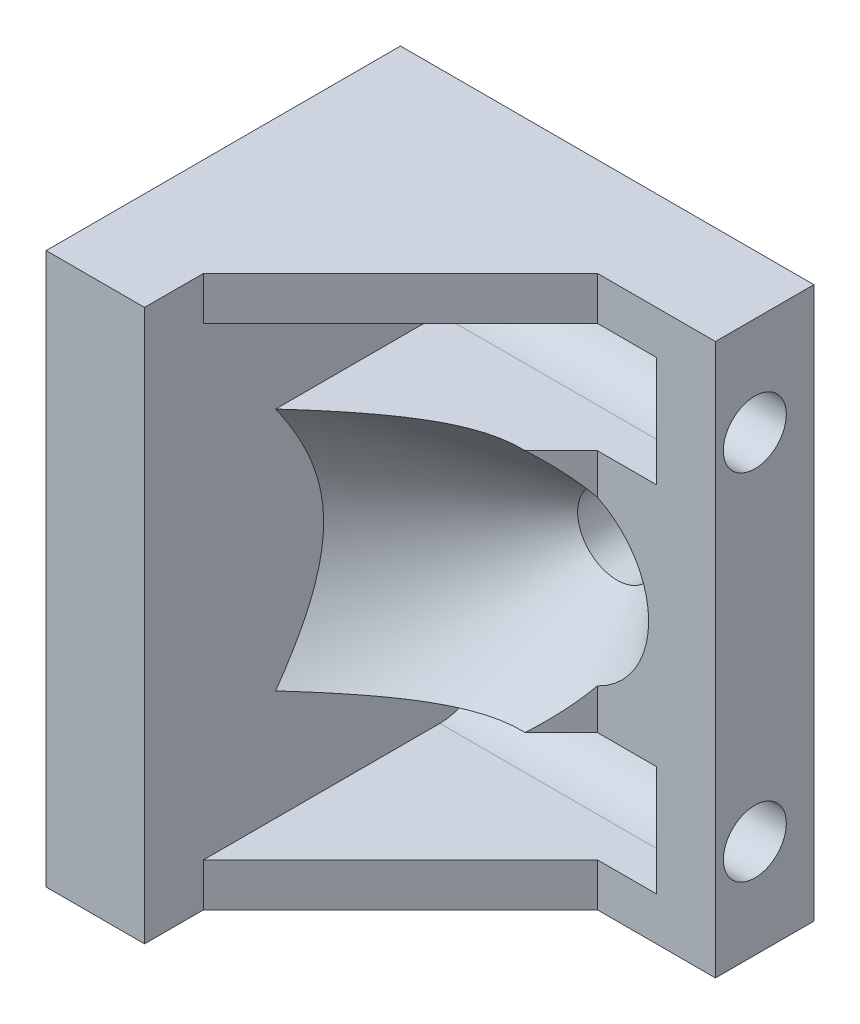
SolidWorks part; units mm, degrees
ref_plane "Front Plane" through (0, 0, 0) normal (0, 0, 1) x (1, 0, 0)
ref_plane "Top Plane" through (0, 0, 0) normal (0, 1, 0) x (1, 0, 0)
ref_plane "Right Plane" through (0, 0, 0) normal (1, 0, 0) x (0, 0, -1)
sketch "Sketch1" plane through (0, 0, 0) normal (0, 0, 1) x (1, 0, 0)
  line L1 (-8, 14) -> (8, 14)
  line L2 (-8, 14) -> (-8, -14)
  line L3 (-8, -14) -> (8, -14)
  line L4 (8, 14) -> (8, -14)
  line L5 (-8, 14) -> (8, -14) construction
  line L6 (-8, -14) -> (8, 14) construction
  circle A0 centre (0, 0) radius 2
  point P0 (0, 0)
extrude "Boss-Extrude1" add sketch "Sketch1" along normal blind 5
sketch "Sketch2" plane through (0, 0, 5) normal (0, 0, 1) x (1, 0, 0)
  circle A0 centre (0, 0) radius 4
chamfer "Chamfer1" distance 3 angle 41 1 edges at (2, 0, 5) first distance on face at (2, 0, 5)
ref_plane "Plane1" through (-8, 0, 0) normal (-1, 0, 0) x (0, 0, 1)
sketch "Sketch3" plane through (-8, 0, 0) normal (-1, 0, 0) x (0, 0, 1)
  line L0 (0, 14) -> (0, -14)
  line L1 (0, -14) -> (18, -14)
  line L2 (18, -14) -> (18, 14)
  line L3 (18, 14) -> (0, 14)
  line L4 (18, -14) -> (18, -10.3194) construction
  line L5 (18, -10.3194) -> (-12, -10.3194) construction
  line L6 (0, -14) -> (-12, -14) construction
  line L7 (-12, -14) -> (-12, 14) construction
  line L8 (-12, 14) -> (0, 14) construction
  line L9 (18, 0) -> (3, 0) construction
  line L10 (18, 14) -> (21.0855, 14) construction
  line L11 (21.0855, 14) -> (21.0855, 6) construction
  point P4 (0, 0)
extrude "Boss-Extrude2" add sketch "Sketch3" along normal blind 5
sketch "Sketch5" plane through (-8, 0, 0) normal (-1, 0, 0) x (0, 0, 1)
  line L0 (18, 0) -> (3, 0) construction
  line L1 (18, -14) -> (18, 14) construction
  line L2 (3, 14) -> (3, 9) construction
  line L3 (5, 14) -> (0, 14) construction
  line L4 (3, -11.8) -> (5.8, -11.8)
  line L5 (5.8, -11.8) -> (5.8, -6.2)
  line L6 (5.8, -6.2) -> (3, -6.2)
  line L7 (3, 6.2) -> (5.8, 6.2)
  line L8 (5.8, 6.2) -> (5.8, 11.8)
  line L9 (5.8, 11.8) -> (3, 11.8)
  circle A0 centre (3, 9) radius 2.8
  circle A1 centre (3, -9) radius 2.8
extrude "Cut-Extrude2" cut sketch "Sketch5" against normal blind 13 contours A1 | L6 A1 L5 | L5 A1 L4 | A0 | A0 L8 L9 | A0 L7 L8 region at (-8, -11.1746, 5.1746) region at (-8, -9, 3) region at (-8, -6.8254, 5.1746) region at (-8, 6.8254, 5.1746) region at (-8, 9, 3) region at (-8, 11.1746, 5.1746)
sketch "Sketch6" plane through (-8, 0, 0) normal (1, 0, 0) x (0, 0, -1)
  circle A0 centre (-3, -9) radius 1.6
  circle A1 centre (-3, 9) radius 1.6
extrude "Cut-Extrude3" cut sketch "Sketch6" against normal through all both and the other way through all
chamfer "Chamfer2" distance 10 angle 45 3 edges at (-8, 12.9, 5) (-8, -12.9, 5) (-8, 0, 5)
